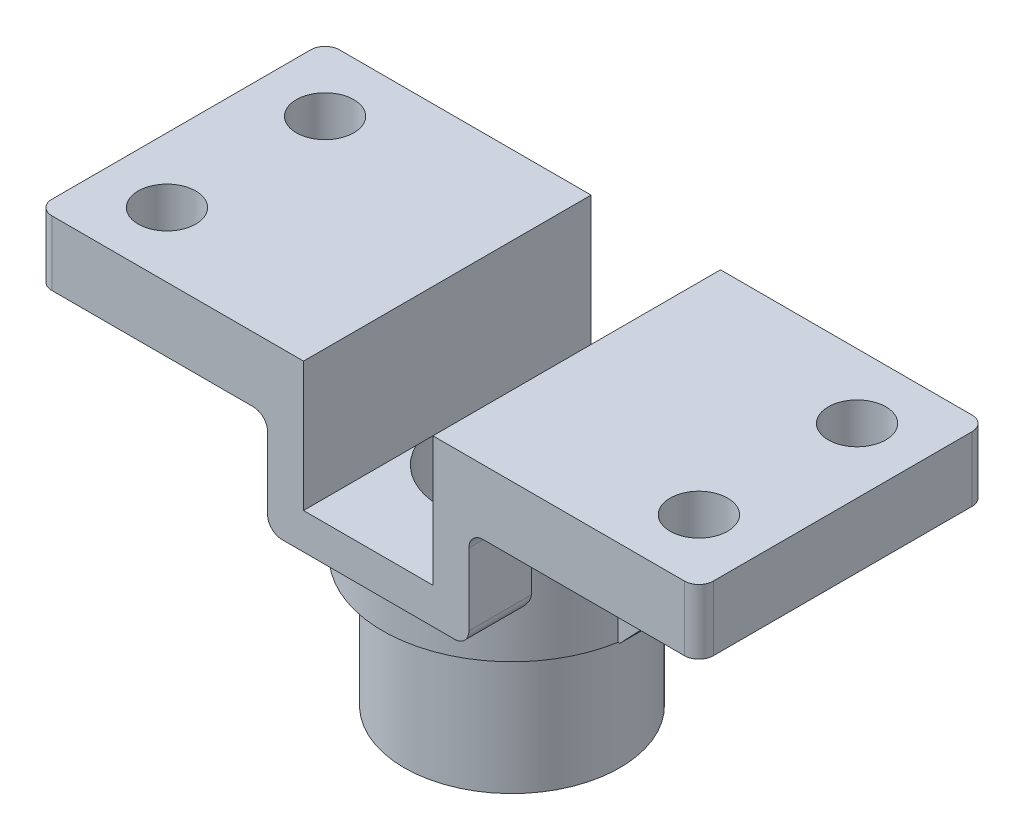
SolidWorks part; units mm, degrees
ref_plane "Front Plane" through (0, 0, 0) normal (0, 0, 1) x (1, 0, 0)
ref_plane "Top Plane" through (0, 0, 0) normal (0, 1, 0) x (1, 0, 0)
ref_plane "Right Plane" through (0, 0, 0) normal (1, 0, 0) x (0, 0, -1)
sketch "Sketch1" plane through (0, 0, 0) normal (0, 1, 0) x (1, 0, 0)
  line L0 (0, 0) -> (0, 38.9887) construction
  line L1 (46, 20) -> (-46, 20)
  line L2 (46, 20) -> (46, -20)
  line L3 (46, -20) -> (-46, -20)
  line L4 (-46, 20) -> (-46, -20)
  line L5 (0, 0) -> (-66.9866, 0) construction
  line L6 (-37, 11) -> (-37, -11) construction
  line L7 (37, 11) -> (37, -11) construction
  circle A0 centre (-37, 11) radius 4
  circle A1 centre (-37, -11) radius 4
  circle A2 centre (37, -11) radius 4
  circle A3 centre (37, 11) radius 4
  dimension "D5" = 8
  dimension "D1" = 92
  dimension "D2" = 40
  dimension "D3" = 9
  dimension "D4" = 9
  dimension "D6" = 9
extrude "Boss-Extrude2" add sketch "Sketch1" along normal blind 9
sketch "Sketch3" plane through (0, 0, 0) normal (0, -1, 0) x (1, 0, 0)
  circle A0 centre (0, 0) radius 10
  circle A1 centre (0, 0) radius 18
  dimension "D1" = 20
  dimension "D2" = 36
extrude "Boss-Extrude3" add sketch "Sketch3" along normal blind 20
sketch "Sketch4" plane through (0, -20, 0) normal (0, -1, 0) x (1, 0, 0)
  circle A0 centre (0, 0) radius 15
  circle A1 centre (0, 0) radius 10
  dimension "D1" = 30
  dimension "D2" = 20
extrude "Boss-Extrude4" add sketch "Sketch4" along normal blind 18
sketch "Sketch8" plane through (0, 0, 20) normal (0, 0, 1) x (1, 0, 0)
  line L0 (-46, 9) -> (46, 9) construction
  line L1 (-9, -9) -> (9, -9)
  line L2 (-9, -9) -> (-9, 9)
  line L3 (-9, 9) -> (9, 9)
  line L4 (9, -9) -> (9, 9)
  line L5 (0, 0) -> (0, -15.1568) construction
  line L6 (0, 0) -> (30.7095, 0) construction
  dimension "D1" = 18
  dimension "D2" = 18
extrude "Cut-Extrude1" cut sketch "Sketch8" against normal up to next
sketch "Sketch9" plane through (0, 0, 20) normal (0, 0, 1) x (1, 0, 0)
  line L1 (-14, 0) -> (14, 0)
  line L2 (-14, 0) -> (-14, -14)
  line L3 (-14, -14) -> (14, -14)
  line L4 (14, 0) -> (14, -14)
  line L5 (-46, 0) -> (-9, 0) construction
  line L6 (0, 0) -> (0, -36.485) construction
  dimension "D1" = 14
  dimension "D2" = 28
extrude "Cut-Extrude2" cut sketch "Sketch9" against normal up to next
sketch "Sketch10" plane through (0, 0, 20) normal (0, 0, 1) x (1, 0, 0)
  line L0 (9, 0) -> (9, -9)
  line L1 (9, 0) -> (9, 9) construction
  line L2 (9, 0) -> (46, 0) construction
  line L3 (9, -9) -> (-8.8813, -9)
  line L4 (-8.8813, -9) -> (-9, 0)
  line L5 (9, 0) -> (14, 0)
  line L6 (14, 0) -> (14, -14)
  line L7 (14, -14) -> (-14, -14)
  line L8 (-14, -14) -> (-14, 0)
  line L9 (-14, 0) -> (-9, 0)
  dimension "D1" = 5
extrude "Boss-Extrude5" add sketch "Sketch10" against normal up to surface (40 mm away) up to face at (27.5, 4.5, -20)
sketch "Sketch13" plane through (0, 0, 0) normal (0, 0, 1) x (1, 0, 0)
  line L0 (-18, -20) -> (-37, 0)
  line L1 (-46, 0) -> (-14, 0) construction
  line L2 (-37, 0) -> (-18, 0)
  line L4 (0, 0) -> (0, -48.4599) construction
  line L5 (-46, 9) -> (-46, 0) construction
  line L6 (37, 0) -> (18, 0)
  line L8 (18, -20) -> (37, 0)
  line L9 (-18, -20) -> (18, -20) construction
  line L10 (-18, -20) -> (18, -20)
  line L12 (18, 0) -> (9, 0)
  line L13 (9, -9) -> (9, 9) construction
  line L14 (-18, 0) -> (-9, 0)
  line L15 (-9, 0) -> (9, 0)
  dimension "D1" = 9
extrude "Boss-Extrude9" add sketch "Sketch13" along normal mid plane 6
extrude "Cut-Extrude5" cut sketch "Sketch8<3>" against normal up to next
sketch "Sketch8<3>" plane through (0, 0, 20) normal (0, 0, 1) x (1, 0, 0) same geometry as "Sketch8"
sketch "Sketch18" plane through (0, -20, 0) normal (0, -1, 0) x (1, 0, 0)
  line L2 (9.5394, 3) -> (-9.5394, 3)
  line L3 (-9.5394, -3) -> (9.5394, -3)
  line L4 (9.5394, 3) -> (-9.5394, 3)
  line L5 (-9.5394, -3) -> (9.5394, -3)
  arc A2 (9.5394, -3) -> (9.5394, 3) centre (0, 0) ccw
  arc A3 (-9.5394, 3) -> (-9.5394, -3) centre (0, 0) ccw
  arc A4 (9.5394, -3) -> (9.5394, 3) centre (0, 0) ccw
  arc A5 (-9.5394, 3) -> (-9.5394, -3) centre (0, 0) ccw
  dimension "D1" = 0
extrude "Cut-Extrude6" cut sketch "Sketch18" against normal blind 6
sketch "Sketch19" plane through (0, -14, 0) normal (0, -1, 0) x (1, 0, 0)
  circle A1 centre (0, 0) radius 10
  circle A2 centre (0, 0) radius 10
  dimension "D1" = 0
extrude "Cut-Extrude7" cut sketch "Sketch19" against normal up to surface (5 mm away) up to face at (0, -9, 0)
fillet "Fillet1" radius 2 4 edges at (46, 4.5, 20) (-46, 4.5, 20) (-46, 4.5, -20) (46, 4.5, -20)
fillet "Fillet2" radius 2 8 edges at (14, 0, -15.6569) (14, 0, 15.6569) (-14, 0, 15.6569) (-14, 0, -15.6569) (-14, -14, -15.6569) (-14, -14, 15.6569) (14, -14, 15.6569) (14, -14, -15.6569)
